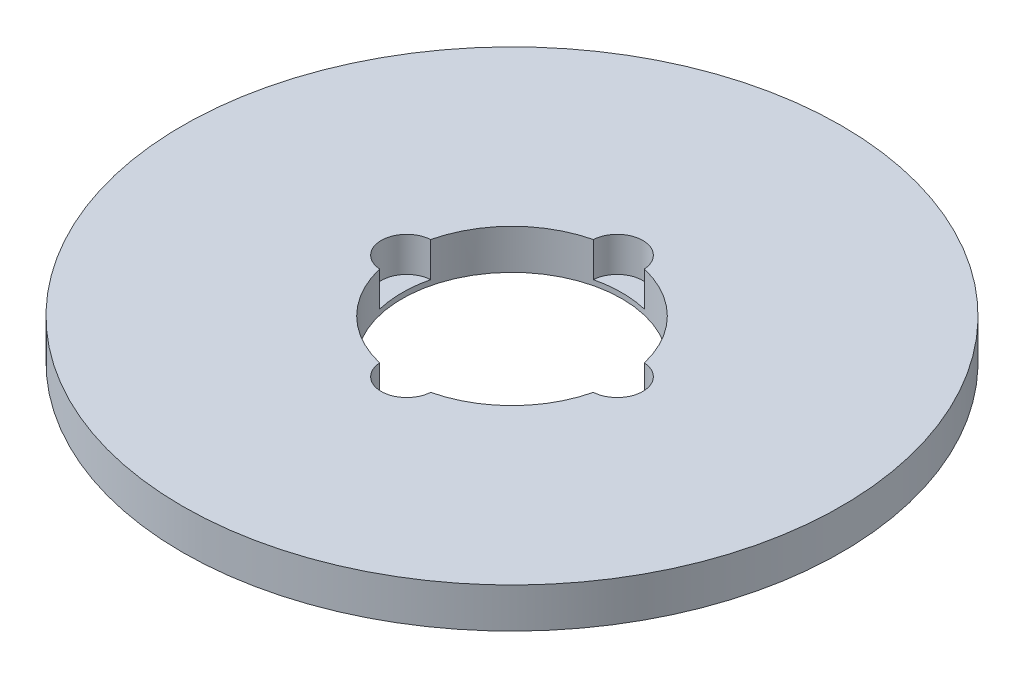
SolidWorks part; units mm, degrees
ref_plane "Front Plane" through (0, 0, 0) normal (0, 0, 1) x (1, 0, 0)
ref_plane "Top Plane" through (0, 0, 0) normal (0, 1, 0) x (1, 0, 0)
ref_plane "Right Plane" through (0, 0, 0) normal (1, 0, 0) x (0, 0, -1)
sketch "Sketch1" plane through (0, 0, 0) normal (0, 1, 0) x (1, 0, 0)
  circle A0 centre (0, 0) radius 82.5
  dimension "FLANGE_OD" = 165
extrude "Boss-Extrude1" add sketch "Sketch1" along normal blind 10
sketch "Sketch2" plane through (0, 0, 0) normal (0, 1, 0) x (1, 0, 0)
  circle A0 centre (0, 0) radius 27.5
  dimension "BORE_D" = 55
extrude "Cut-Extrude1" cut sketch "Sketch2" along normal through all
sketch "Sketch3" plane through (0, 10, 0) normal (0, 1, 0) x (1, 0, 0)
  circle A0 centre (0, 0) radius 26.344 construction
  circle A1 centre (-26.344, 0) radius 6.4016
  dimension "BOLT_D" = 12.8033
  dimension "BOLT_PCD" = 52.6881
extrude "Cut-Extrude2" cut sketch "Sketch3" against normal blind 8.6971
pattern_circular "CirPattern1" count 4 over 360 about axis through (0, 0, 0) along (0, 1, 0) of "Cut-Extrude2"
